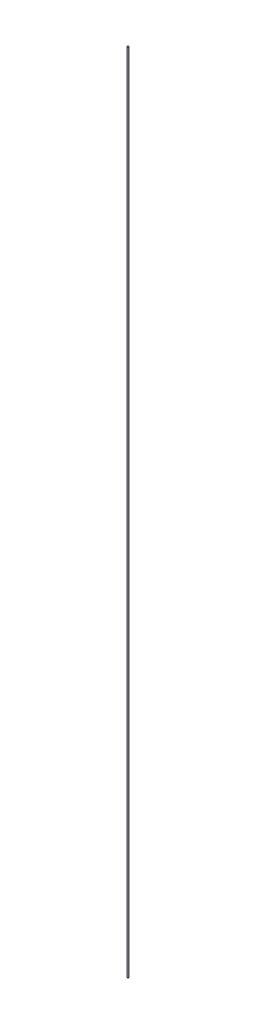
SolidWorks part; units mm, degrees
ref_plane "Front Plane" through (0, 0, 0) normal (0, 0, 1) x (1, 0, 0)
ref_plane "Top Plane" through (0, 0, 0) normal (0, 1, 0) x (1, 0, 0)
ref_plane "Right Plane" through (0, 0, 0) normal (1, 0, 0) x (0, 0, -1)
sketch "Sketch2" plane through (0, 0, 0) normal (0, 1, 0) x (1, 0, 0)
  circle A0 centre (0, 0) radius 1.27
  dimension "D1" = 2.54
extrude "Boss-Extrude3" add sketch "Sketch2" along normal blind 1282.7
